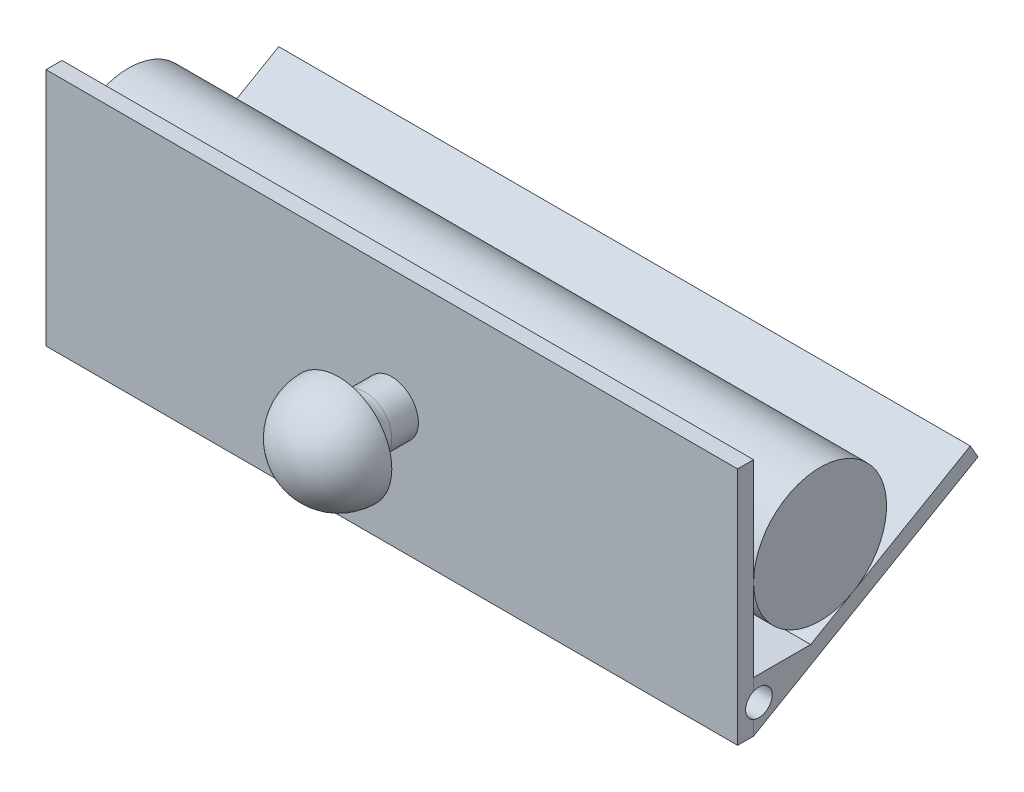
SolidWorks part; units mm, degrees
ref_plane "Front Plane" through (0, 0, 0) normal (0, 0, 1) x (1, 0, 0)
ref_plane "Top Plane" through (0, 0, 0) normal (0, 1, 0) x (1, 0, 0)
ref_plane "Right Plane" through (0, 0, 0) normal (1, 0, 0) x (0, 0, -1)
sketch "Sketch1" plane through (0, 0, 0) normal (0, 0, 1) x (1, 0, 0)
  line L1 (0, 0) -> (130, 0)
  line L2 (0, 0) -> (0, 45)
  line L3 (0, 45) -> (130, 45)
  line L4 (130, 0) -> (130, 45)
  dimension "D1" = 130
  dimension "D2" = 45
extrude "Boss-Extrude1" add sketch "Sketch1" along normal blind 3
sketch "Sketch3" plane through (0, 0, 3) normal (0, 0, 1) x (1, 0, 0)
  line L0 (130, 45) -> (0, 45) construction
  line L1 (130, 0) -> (130, 45) construction
  circle A0 centre (65, 22.5) radius 10
  point P2 (0, 0)
  point P5 (65, 45)
  point P8 (130, 22.5)
  dimension "D1" = 20
extrude "Boss-Extrude2" add sketch "Sketch3" along normal blind 20
fillet "Fillet1" radius 10 1 edges at (75, 22.5, 23)
sketch "Sketch4" plane through (0, 0, 3) normal (0, 0, 1) x (1, 0, 0)
  circle A0 centre (65, 22.5) radius 10
  circle A1 centre (65, 22.5) radius 5
  dimension "D1" = 20
  dimension "D2" = 10
extrude "Cut-Extrude3" cut sketch "Sketch4" along normal blind 10 from surface contours A0 | A1 starting at face at (55, 22.5, 3)
fillet "Fillet2" radius 5 1 edges at (60, 22.5, 13)
sketch "Sketch5" plane through (0, 0, 0) normal (-1, 0, 0) x (0, 0, 1)
  line L0 (0, 45) -> (0, 0) construction
  line L1 (0, 0) -> (-42.188, 24.3572)
  line L2 (-10.7307, 9.5448) -> (-40.7377, 26.8693)
  line L3 (-40.7377, 26.8693) -> (-42.188, 24.3572)
  line L5 (-10.7307, 9.5448) -> (0, 9.5448)
  line L6 (0, 0) -> (0, 9.5448)
  circle A0 centre (-12.5, 25) radius 12.5
  line M2 (0, 45) -> (0, 0)
  dimension "D1" = 25
  dimension "D2" = 60
extrude "Boss-Extrude3" add sketch "Sketch5" against normal blind 130 separate body contours A0 | L5 L2 L3 L1 M2 region at (0, 12.4466, -17.4201) region at (0, 25, -12.5)
sketch "Sketch6" plane through (0, 0, 0) normal (-1, 0, 0) x (0, 0, 1)
  line L0 (0, 9.5448) -> (0, 0) construction
  line L1 (3, 45) -> (3, 0) construction
  line L2 (3, 0) -> (0, 0) construction
  circle A0 centre (-1, 5) radius 2.5
  point P2 (0, 0)
  point P5 (0, 4.7724)
  point P8 (0, 0)
  dimension "D1" = 5
  dimension "D2" = 4
  dimension "D3" = 5
extrude "Cut-Extrude4" cut sketch "Sketch6" against normal blind 130
